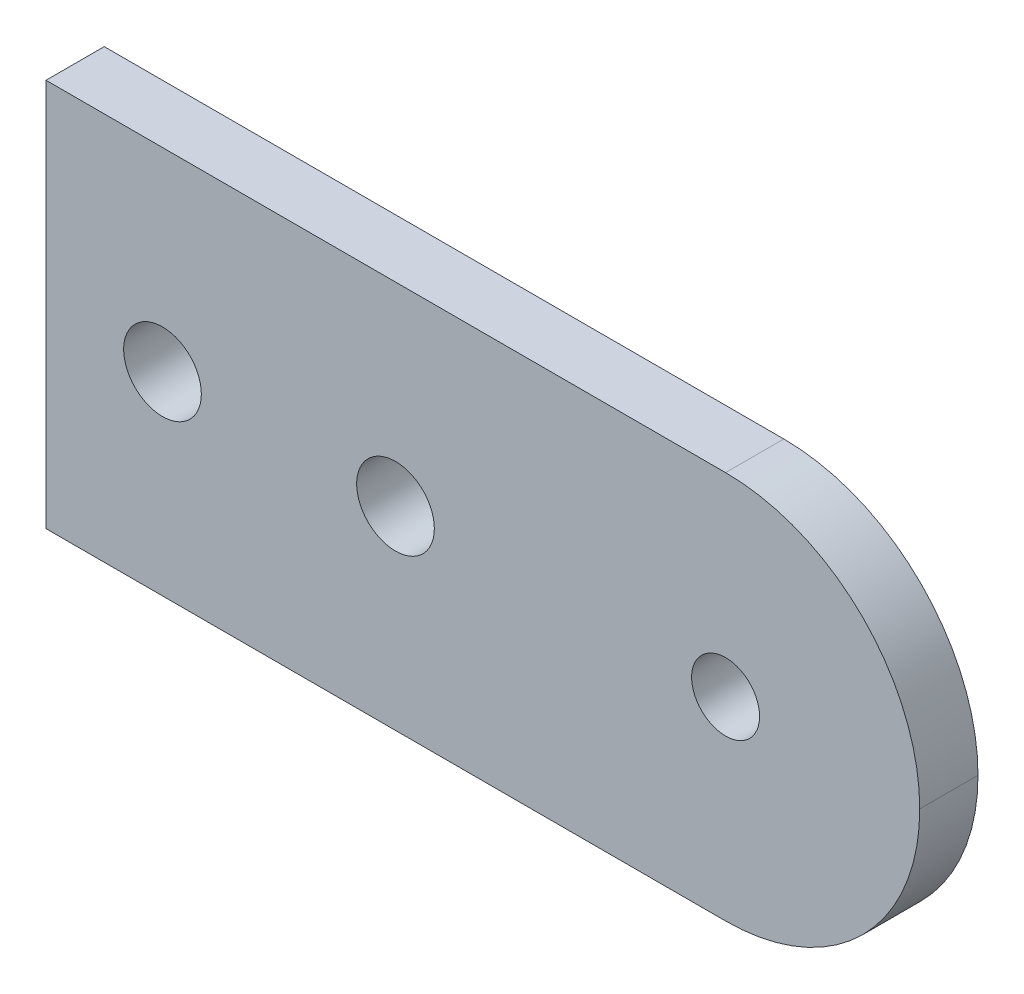
SolidWorks part; units mm, degrees
ref_plane "Plano frontal" through (0, 0, 0) normal (0, 0, 1) x (1, 0, 0)
ref_plane "Plano superior" through (0, 0, 0) normal (0, 1, 0) x (1, 0, 0)
ref_plane "Plano direito" through (0, 0, 0) normal (1, 0, 0) x (0, 0, -1)
sketch "Esboço1" plane through (0, 0, 0) normal (0, 0, 1) x (1, 0, 0)
  line L0 (-16.5, 10) -> (-16.5, -10) construction
  line L1 (-22.5, 10) -> (22.5, 10)
  line L2 (-22.5, 10) -> (-22.5, -10)
  line L3 (-22.5, -10) -> (22.5, -10)
  line L4 (22.5, 10) -> (22.5, -10)
  line L5 (-22.5, 10) -> (22.5, -10) construction
  line L6 (-22.5, -10) -> (22.5, 10) construction
  line L7 (-4.5, 10) -> (-4.5, -10) construction
  line L8 (22.5, 0) -> (12.5, 0) construction
  circle A0 centre (-16.5, 0) radius 2
  circle A1 centre (-4.5, 0) radius 2
  circle A2 centre (12.5, 0) radius 1.75
  point P0 (0, 0)
  dimension "D5" = 4
  dimension "D7" = 3.5
  dimension "D1" = 20
  dimension "D2" = 45
  dimension "D6" = 10
  dimension "D3" = 6
  dimension "D4" = 12
extrude "Ressalto-extrusão1" add sketch "Esboço1" along normal blind 3
ref_plane "Plano1" through (0, 0, 0) normal (0, 1, 0) x (1, 0, 0)
fillet "Filete1" radius 10 2 edges at (22.5, -10, 1.5) (22.5, 10, 1.5)
